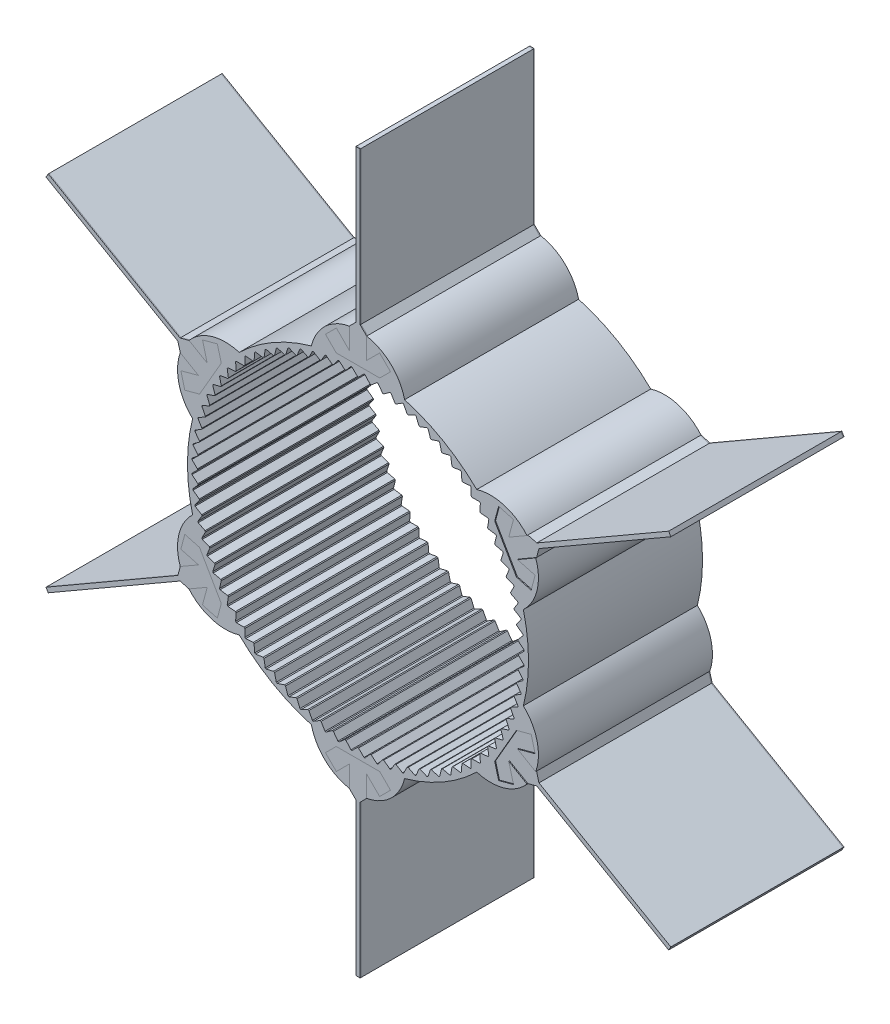
SolidWorks part; units mm, degrees
ref_plane "Front Plane" through (0, 0, 0) normal (0, 0, 1) x (1, 0, 0)
ref_plane "Top Plane" through (0, 0, 0) normal (0, 1, 0) x (1, 0, 0)
ref_plane "Right Plane" through (0, 0, 0) normal (1, 0, 0) x (0, 0, -1)
sketch "Sketch1" plane through (0, 0, 0) normal (0, 0, 1) x (1, 0, 0)
  circle A0 centre (0, 0) radius 76.3944
  circle A1 centre (0, 0) radius 78.3944
  dimension "D1" = 152.7887
  dimension "D2" = 2
extrude "Boss-Extrude1" add sketch "Sketch1" along normal blind 80
sketch "Sketch2" plane through (0, 0, 0) normal (0, 0, -1) x (-1, 0, 0)
  line L0 (-2.7494, 76.3449) -> (-0.2494, 73.8449)
  line L1 (-0.2494, 73.8449) -> (0.2494, 73.8449)
  line L2 (0.2494, 73.8449) -> (2.7494, 76.3449)
  line L3 (-2.7494, 76.3449) -> (2.7494, 76.3449) construction
  circle A0 centre (0, 0) radius 76.3944 construction
  arc A1 (-2.7494, 76.3449) -> (2.7494, 76.3449) centre (0, 0) cw
  point P7 (0, 76.3449)
  point P9 (0, 73.8449)
  dimension "D1" = 45
  dimension "D3" = 2.5
  dimension "D2" = 5.5
extrude "Boss-Extrude2" add sketch "Sketch2" against normal up to surface (80 mm away) up to face at (78.3944, 0, 80)
pattern_circular "CirPattern1" count 80 over 360 about axis through (0, 0, 0) along (0, 0, 1) of "Boss-Extrude2"
sketch "Sketch3" plane through (0, 0, 0) normal (0, 0, -1) x (-1, 0, 0)
  line L0 (0, 70.3944) -> (0, 78.3944) construction
  line L1 (0, 78.3944) -> (0, 92.3944) construction
  arc A0 (-21.4204, 75.4112) -> (21.4204, 75.4112) centre (0, 70.3944) cw
  circle A1 centre (0, 0) radius 78.3944 construction
  arc A2 (-21.4204, 75.4112) -> (21.4204, 75.4112) centre (0, 0) cw
  point P7 (0, 92.3944)
  dimension "D1" = 22
  dimension "D2" = 14
extrude "Boss-Extrude3" add sketch "Sketch3" against normal up to surface (80 mm away) up to face at (78.3944, 0, 80)
sketch "Sketch4" plane through (0, 0, 0) normal (0, 0, -1) x (-1, 0, 0)
  line L0 (-4, 92.0277) -> (-4, 82.3449)
  line L1 (-4, 82.3449) -> (-9.9497, 88.2946)
  line L2 (-9.9497, 88.2946) -> (-14.9497, 83.2946)
  line L3 (-14.9497, 83.2946) -> (-10, 78.3449)
  line L4 (-10, 78.3449) -> (10, 78.3449)
  line L5 (10, 78.3449) -> (14.9497, 83.2946)
  line L6 (14.9497, 83.2946) -> (9.9497, 88.2946)
  line L7 (9.9497, 88.2946) -> (4, 82.3449)
  line L8 (4, 82.3449) -> (4, 92.0277)
  line L9 (-4, 82.3449) -> (4, 82.3449) construction
  line L10 (-0.2494, 73.8449) -> (0.2494, 73.8449) construction
  arc A0 (21.4204, 75.4112) -> (-21.4204, 75.4112) centre (0, 70.3944) ccw construction
  arc A1 (-4, 92.0277) -> (4, 92.0277) centre (0, 70.3944) cw
  point P14 (0, 82.3449)
  point P15 (0, 78.3449)
  dimension "D1" = 8
  dimension "D2" = 4.5
  dimension "D3" = 20
  dimension "D4" = 7
  dimension "D5" = 4
extrude "Cut-Extrude1" cut sketch "Sketch4" against normal up to surface (80 mm away) up to face at (0, 7, 80)
sketch "Sketch6" plane through (0, 0, 0) normal (0, 0, -1) x (-1, 0, 0)
  line L0 (10, 78.3449) -> (14.9497, 83.2946) construction
  line L1 (14.9497, 83.2946) -> (9.9497, 88.2946) construction
  line L2 (9.9497, 88.2946) -> (4, 82.3449) construction
  line L3 (4, 82.3449) -> (4, 92.0277) construction
  line L4 (-4, 92.0277) -> (-4, 82.3449) construction
  line L5 (-4, 82.3449) -> (-9.9497, 88.2946) construction
  line L6 (-10, 78.3449) -> (10, 78.3449) construction
  line L7 (-14.9497, 83.2946) -> (-10, 78.3449) construction
  line L8 (-9.9497, 88.2946) -> (-14.9497, 83.2946) construction
  line L9 (10, 78.3449) -> (14.9497, 83.2946)
  line L10 (14.9497, 83.2946) -> (9.9497, 88.2946)
  line L11 (9.9497, 88.2946) -> (4, 82.3449)
  line L12 (4, 82.3449) -> (4, 92.0277)
  line L13 (-4, 92.0277) -> (-4, 82.3449)
  line L14 (-4, 82.3449) -> (-9.9497, 88.2946)
  line L15 (-10, 78.3449) -> (10, 78.3449)
  line L16 (-14.9497, 83.2946) -> (-10, 78.3449)
  line L17 (-9.9497, 88.2946) -> (-14.9497, 83.2946)
  line L18 (-4, 92.0277) -> (-1, 95.0277)
  line L19 (-1, 95.0277) -> (-1, 165.0277)
  line L20 (-1, 165.0277) -> (1, 165.0277)
  line L21 (1, 165.0277) -> (1, 95.0277)
  line L22 (1, 95.0277) -> (4, 92.0277)
  point P13 (0, 165.0277)
  point P15 (0, 78.3449)
  dimension "D1" = 2
  dimension "D2" = 135
  dimension "D3" = 70
extrude "Boss-Extrude6" add sketch "Sketch6" against normal offset from surface (79.2 mm away) 0.4 from offset 0.4 separate body up to face at (0, 70.9016, 80) offset against normal yes
pattern_circular "CirPattern2" count 6 over 360 about axis through (0, 0, 0) along (0, 0, 1) of "Boss-Extrude3", "Cut-Extrude1"
pattern_circular "CirPattern5" count 6 over 360 about axis through (0, 0, 0) along (0, 0, 1) of bodies 108
ref_plane "Plane1" through (0, 0, 40) normal (0, 0, -1) x (-1, 0, 0)
extrude "Boss-Extrude7" add sketch "Sketch6<2>" against normal blind 0.4 separate body
sketch "Sketch6<2>" plane through (0, 0, 0) normal (0, 0, -1) x (-1, 0, 0) same geometry as "Sketch6"
pattern_circular "CirPattern7" count 6 over 360 about axis through (0, 0, 0) along (0, 0, 1) of bodies 115
mirror "Mirror1" about plane through (0, 0, 40) normal (0, 0, -1) of bodies 118 115 116 117
equation "\"hb\"= 4.5mm"
equation "\"ht\"= 2.5mm"
equation "\"pitch\"= 6mm"
equation "\"bt\"= 5.5mm"
equation "\"tooth_angle\"= 45deg"
equation "\"circumference\"= \"pitch\" * \"num_teeth\""
equation "\"diameter\"= \"circumference\" / pi"
equation "\"D1@Sketch1\"=\"diameter\""
equation "\"D2@Sketch1\"= \"hb\" - \"ht\""
equation "\"width\"= 80mm"
equation "\"D1@Boss-Extrude1\"= \"width\""
equation "\"D2@Sketch2\"= \"bt\""
equation "\"D1@Sketch2\"=\"tooth_angle\""
equation "\"D3@Sketch2\"=\"ht\""
equation "\"num_teeth\"= 80"
equation "\"D1@CirPattern1\"=\"num_teeth\""
equation "\"D2@CirPattern1\"= 360 / \"num_teeth\""
equation "\"D2@Sketch4\"= \"hb\""
equation "\"endcap_thickness\"= 0.4mm"
equation "\"D19@Boss-Extrude6\"= \"endcap_thickness\""
equation "\"D1@Boss-Extrude6\"= \"endcap_thickness\""
equation "\"D1@Boss-Extrude7\"=\"endcap_thickness\""
equation "\"num_flaps\"= 6"
equation "\"D1@CirPattern2\"=\"num_flaps\""
equation "\"D1@CirPattern5\"=\"num_flaps\""
equation "\"D1@CirPattern7\"=\"num_flaps\""
